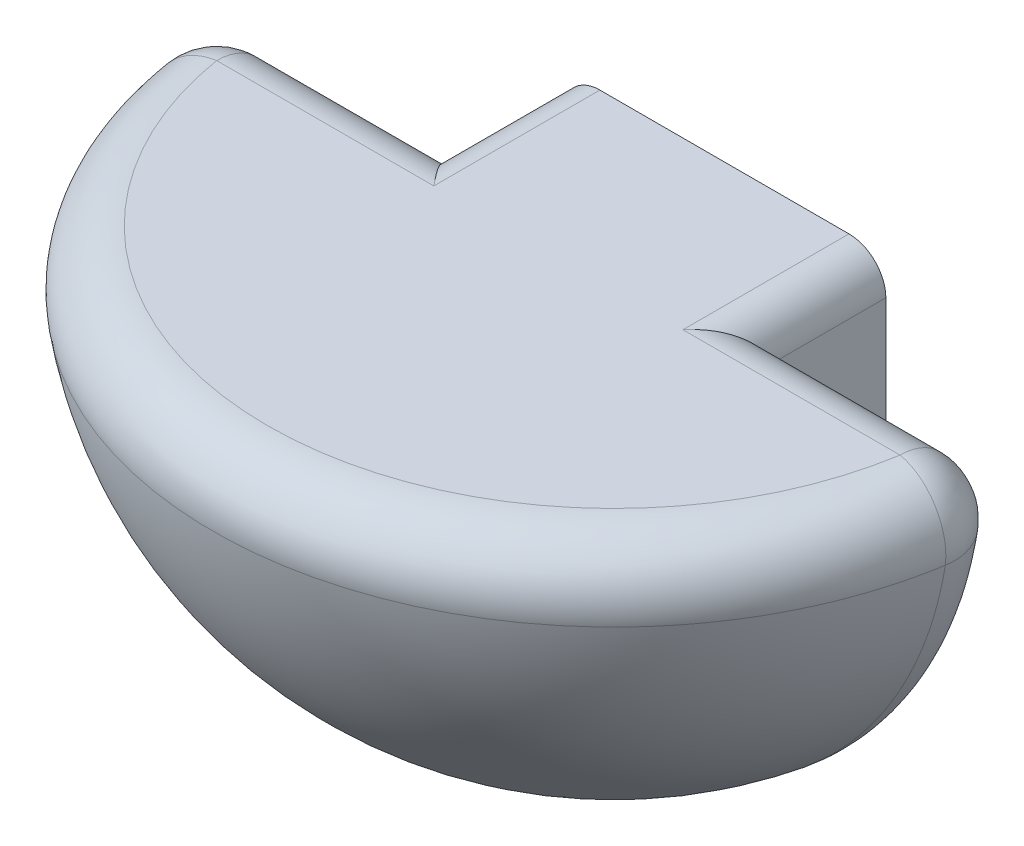
SolidWorks part; units mm, degrees
ref_plane "Front Plane" through (0, 0, 0) normal (0, 0, 1) x (1, 0, 0)
ref_plane "Top Plane" through (0, 0, 0) normal (0, 1, 0) x (1, 0, 0)
ref_plane "Right Plane" through (0, 0, 0) normal (1, 0, 0) x (0, 0, -1)
sketch "Sketch1" plane through (0, 0, 0) normal (0, 0, 1) x (1, 0, 0)
  line L0 (11, 0) -> (-11, 0)
  arc A0 (-11, 0) -> (11, 0) centre (0, 0) ccw
  dimension "D1" = 22
revolve "Revolve1" add sketch "Sketch1" angle 90 about L0
sketch "Sketch2" plane through (0, 0, 0) normal (0, 0, -1) x (-1, 0, 0)
  line L0 (-11, 0) -> (11, 0) construction
  line L1 (-4.375, 0) -> (4.375, 0)
  line L2 (-4.375, 0) -> (-4.375, -8.75)
  line L3 (-4.375, -8.75) -> (4.375, -8.75)
  line L4 (4.375, 0) -> (4.375, -8.75)
  line L6 (-2.375, -2) -> (2.375, -2)
  line L7 (-2.375, -2) -> (-2.375, -6.75)
  line L8 (-2.375, -6.75) -> (2.375, -6.75)
  line L9 (2.375, -2) -> (2.375, -6.75)
  dimension "D1" = 8.75
  dimension "D2" = 4.375
  dimension "D3" = 8.75
  dimension "D4" = 2
  dimension "D5" = 2
  dimension "D6" = 2
  dimension "D7" = 2
extrude "Boss-Extrude1" add sketch "Sketch2" along normal blind 3
fillet "Fillet1" radius 1.5 4 edges at (0, -11, 0) (-7.6875, 0, 0) (7.6875, 0, 0) (0, 0, 11)
fillet "Fillet3" radius 1 4 edges at (-2.375, -2, -1.5) (2.375, -2, -1.5) (-2.375, -6.75, -1.5) (2.375, -6.75, -1.5)
fillet "Fillet4" radius 1 4 edges at (-4.375, 0, -0.75) (-4.375, -8.75, -1.4726) (4.375, -8.75, -1.4726) (4.375, 0, -0.75)
sketch "Sketch6" plane through (0, 0, -3) normal (0, 0, -1) x (-1, 0, 0)
  line L0 (-1.375, -6.75) -> (1.375, -6.75) construction
  line L1 (2.375, -5.75) -> (2.375, -3) construction
  line L2 (1.375, -2) -> (-1.375, -2) construction
  line L3 (-2.375, -3) -> (-2.375, -5.75) construction
  line L4 (-1.375, -6.75) -> (1.375, -6.75)
  line L5 (2.375, -5.75) -> (2.375, -3)
  line L6 (1.375, -2) -> (-1.375, -2)
  line L7 (-2.375, -3) -> (-2.375, -5.75)
  arc A0 (-2.375, -5.75) -> (-1.375, -6.75) centre (-1.375, -5.75) ccw construction
  arc A1 (1.375, -6.75) -> (2.375, -5.75) centre (1.375, -5.75) ccw construction
  arc A2 (2.375, -3) -> (1.375, -2) centre (1.375, -3) ccw construction
  arc A3 (-1.375, -2) -> (-2.375, -3) centre (-1.375, -3) ccw construction
  arc A4 (-2.375, -5.75) -> (-1.375, -6.75) centre (-1.375, -5.75) ccw
  arc A5 (1.375, -6.75) -> (2.375, -5.75) centre (1.375, -5.75) ccw
  arc A6 (2.375, -3) -> (1.375, -2) centre (1.375, -3) ccw
  arc A7 (-1.375, -2) -> (-2.375, -3) centre (-1.375, -3) ccw
extrude "Cut-Extrude3" cut sketch "Sketch6" against normal blind 7.5
